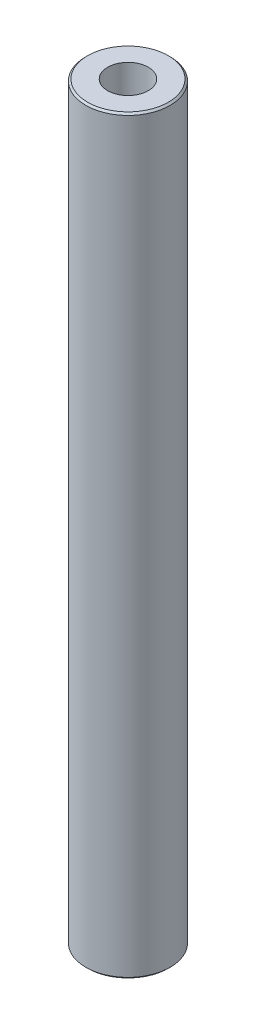
SolidWorks part; units mm, degrees
ref_plane "Front Plane" through (0, 0, 0) normal (0, 0, 1) x (1, 0, 0)
ref_plane "Top Plane" through (0, 0, 0) normal (0, 1, 0) x (1, 0, 0)
ref_plane "Right Plane" through (0, 0, 0) normal (1, 0, 0) x (0, 0, -1)
sketch "Sketch1" plane through (0, 0, 0) normal (0, 1, 0) x (1, 0, 0)
  circle A0 centre (0, 0) radius 30
  dimension "SHAFT_OD" = 60
extrude "Boss-Extrude1" add sketch "Sketch1" along normal blind 533.6842
sketch "Sketch2" plane through (0, 0, 0) normal (0, 1, 0) x (1, 0, 0)
  circle A0 centre (0, 0) radius 14.4749
  dimension "BORE_D" = 28.9498
extrude "Cut-Extrude1" cut sketch "Sketch2" along normal through all
chamfer "Chamfer1" distance 1.2855 angle 45 2 edges at (0, 533.6842, 30) (0, 0, 30)
